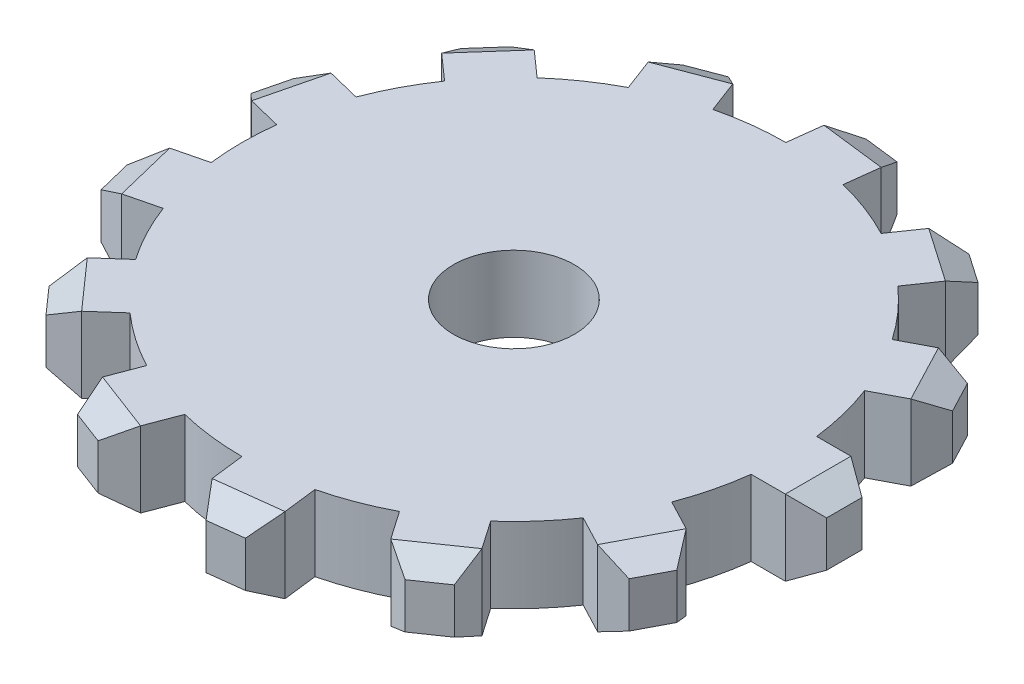
SolidWorks part; units mm, degrees
ref_plane "Front Plane" through (0, 0, 0) normal (0, 0, 1) x (1, 0, 0)
ref_plane "Top Plane" through (0, 0, 0) normal (0, 1, 0) x (1, 0, 0)
ref_plane "Right Plane" through (0, 0, 0) normal (1, 0, 0) x (0, 0, -1)
sketch "Sketch1" plane through (0, 0, 0) normal (0, 1, 0) x (1, 0, 0)
  circle A0 centre (0, 0) radius 9
  circle A1 centre (0, 0) radius 2
  dimension "D1" = 18
  dimension "D2" = 4
extrude "Boss-Extrude1" add sketch "Sketch1" along normal blind 2.5
sketch "Sketch2" plane through (0, 2.5, 0) normal (0, 1, 0) x (1, 0, 0)
  line L0 (0, 9) -> (0.2411, 10.9854)
  line L1 (0.2411, 10.9854) -> (2.3949, 10.7239)
  line L2 (2.3949, 10.7239) -> (2.1538, 8.7385)
  circle A0 centre (0, 0) radius 9 construction
  circle A2 centre (0, 0) radius 9
  arc A3 (2.1538, 8.7385) -> (0, 9) centre (0, 0) ccw
  dimension "D1" = 13.846
  dimension "D2" = 2
  dimension "D3" = 0
extrude "Boss-Extrude2" add sketch "Sketch2" against normal up to surface (2.5 mm away) up to face at (0, 0, 9)
chamfer "Chamfer1" distance 0.5 angle 60 4 edges at (1.318, 0, -10.8547) (0.2411, 1.25, -10.9854) (1.318, 2.5, -10.8547) (2.3949, 1.25, -10.7239) first distance on face at (1.318, 1.25, -10.8547)
pattern_circular "CirPattern1" count 13 over 360 about axis through (0, 2.5, 0) along (0, 1, 0) of "Boss-Extrude2", "Chamfer1"
